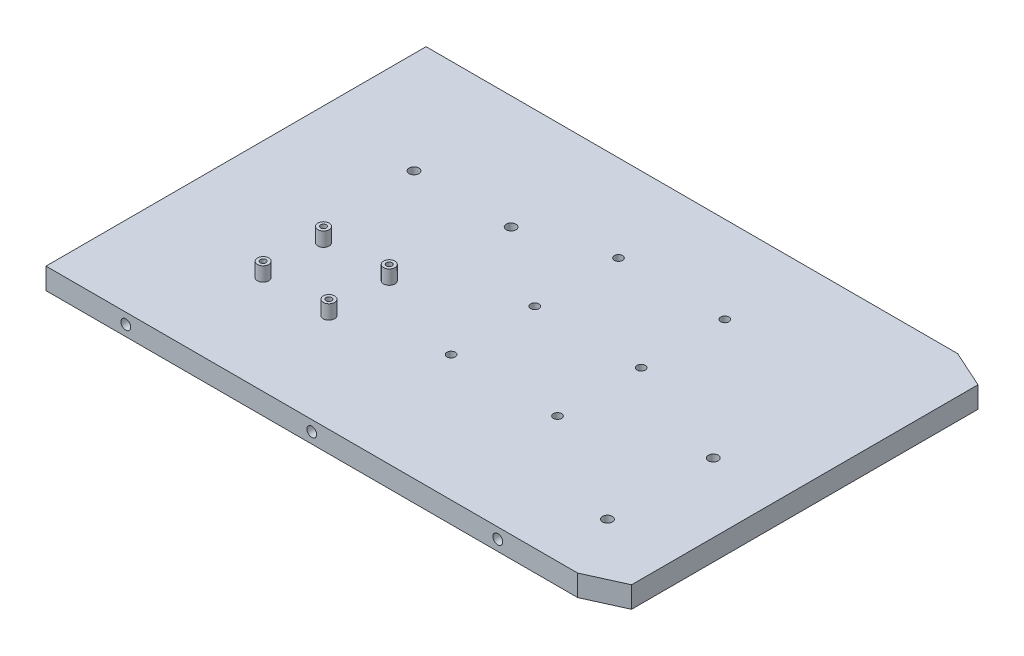
SolidWorks part; units mm, degrees
ref_plane "Front Plane" through (0, 0, 0) normal (0, 0, 1) x (1, 0, 0)
ref_plane "Top Plane" through (0, 0, 0) normal (0, 1, 0) x (1, 0, 0)
ref_plane "Right Plane" through (0, 0, 0) normal (1, 0, 0) x (0, 0, -1)
sketch "Sketch1" plane through (0, 0, 0) normal (0, 1, 0) x (1, 0, 0)
  line L2 (0, 12.0331) -> (0, 268.5969)
  line L6 (374.81, 274.2969) -> (374.81, 268.5969)
  line L9 (401.01, 18.185) -> (401.01, 262.445)
  line L10 (401.01, 262.445) -> (374.81, 274.2969)
  line L12 (374.81, 268.5969) -> (0, 268.5969)
  line L13 (0, 140.315) -> (401.01, 140.315) construction
  line L15 (401.01, 18.185) -> (374.81, 6.3331)
  line L17 (374.81, 12.0331) -> (0, 12.0331)
  line L18 (374.81, 6.3331) -> (374.81, 12.0331)
extrude "Boss-Extrude1" add sketch "Sketch1" along normal blind 10
sketch "Sketch2" plane through (0, 10, 0) normal (0, 1, 0) x (1, 0, 0)
  line L0 (0, 268.5969) -> (0, 12.0331)
  line L1 (352.4341, 121.6803) -> (352.4341, 127.0803) construction
  line L2 (0, 12.0331) -> (374.81, 12.0331)
  line L3 (352.4341, 52.4303) -> (352.4341, 47.0303) construction
  line L4 (374.81, 12.0331) -> (374.81, 6.3331)
  line L5 (374.81, 6.3331) -> (401.01, 18.185)
  line L6 (401.01, 18.185) -> (401.01, 262.445)
  line L7 (401.01, 262.445) -> (374.81, 274.2969)
  line L8 (374.81, 274.2969) -> (374.81, 268.5969)
  line L9 (374.81, 268.5969) -> (0, 268.5969)
  circle A0 centre (271.8499, 154.1197) radius 2.925
  circle A1 centre (271.8499, 213.1197) radius 2.925
  circle A2 centre (271.8499, 95.1197) radius 2.925
  circle A3 centre (196.8499, 95.1197) radius 2.925
  circle A4 centre (196.8499, 154.1197) radius 2.925
  circle A5 centre (196.8499, 213.1197) radius 2.925
  circle A6 centre (140.0829, 194.209) radius 3.45
  circle A7 centre (71.5829, 194.209) radius 3.45
  circle A8 centre (352.4341, 124.3803) radius 3.455
  circle A9 centre (352.4341, 49.7303) radius 3.455
  line M1 (0, 268.5969) -> (0, 12.0331)
extrude "Boss-Extrude3" add sketch "Sketch2" along normal blind 5 contours A4 A3 A0 A1 A2 A5 M1 region at (200.3749, 10, -140.2929)
sketch "Sketch3" plane through (0, 15, 0) normal (0, 1, 0) x (1, 0, 0)
  circle A0 centre (83.5699, 75.8812) radius 2
  circle A1 centre (129.9249, 75.8812) radius 2
  circle A2 centre (129.9249, 118.4262) radius 2
  circle A3 centre (83.5699, 118.4262) radius 2
  circle A4 centre (83.5699, 75.8812) radius 4
  circle A5 centre (83.5699, 118.4262) radius 4
  circle A6 centre (129.9249, 118.4262) radius 4
  circle A8 centre (129.9249, 75.8812) radius 4
extrude "Boss-Extrude4" add sketch "Sketch3" along normal blind 10
sketch "Sketch4" plane through (0, 0, -12.0331) normal (0, 0, 1) x (1, 0, 0)
  line L1 (0, 0) -> (374.81, 0)
  line L2 (0, 0) -> (0, 15)
  line L3 (0, 15) -> (374.81, 15)
  line L4 (374.81, 0) -> (374.81, 15)
  circle A0 centre (187.405, 7.5) radius 3.455
  circle A1 centre (56.2694, 7.5) radius 3.455
  circle A2 centre (318.5406, 7.5) radius 3.455
extrude "Boss-Extrude5" add sketch "Sketch4" along normal blind 5.7
sketch "Sketch5" plane through (0, 0, -268.5969) normal (0, 0, -1) x (-1, 0, 0)
  line L0 (-374.81, 0) -> (0, 0)
  line L1 (-374.81, 0) -> (-374.81, 15)
  line L2 (-374.81, 15) -> (0, 15)
  line L3 (0, 0) -> (0, 15)
  line L4 (-374.81, 15) -> (-374.81, 0) construction
  line L5 (-374.81, 15) -> (-374.81, 0) construction
  circle A0 centre (-187.405, 7.5) radius 3.455
  circle A1 centre (-318.5406, 7.5) radius 3.455
  circle A2 centre (-56.2694, 7.5) radius 3.455
extrude "Boss-Extrude6" add sketch "Sketch5" along normal blind 5.7
